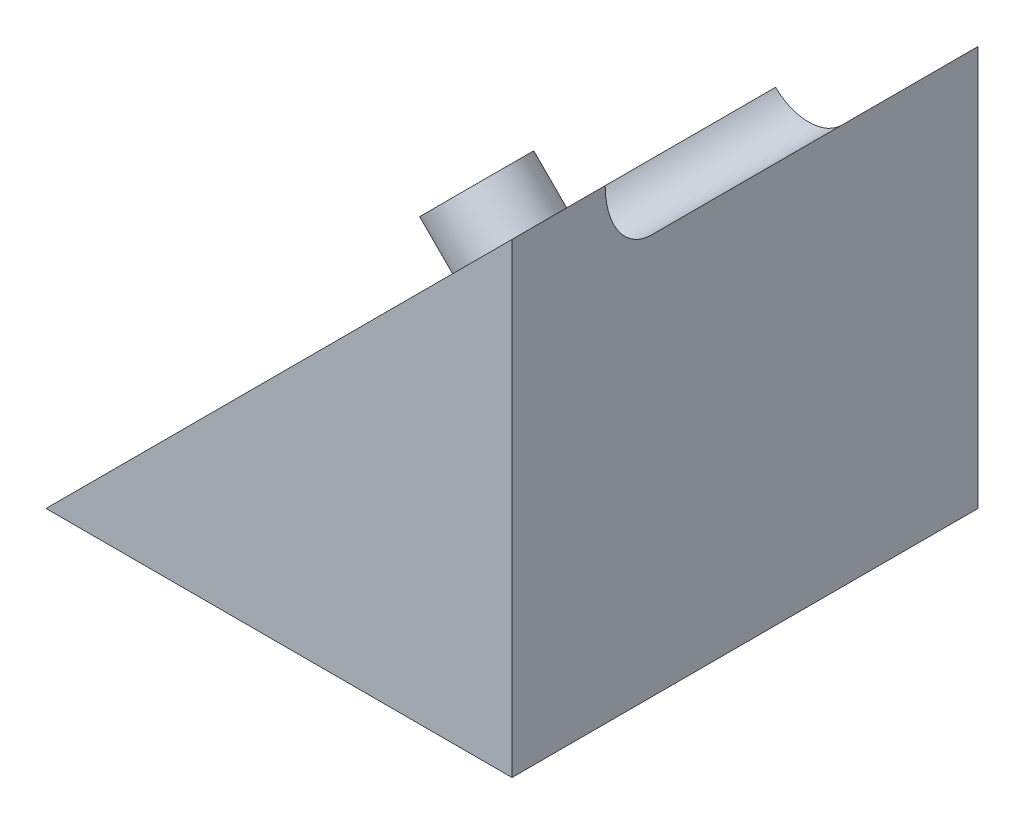
SolidWorks part; units mm, degrees
ref_plane "Front Plane" through (0, 0, 0) normal (0, 0, 1) x (1, 0, 0)
ref_plane "Top Plane" through (0, 0, 0) normal (0, 1, 0) x (1, 0, 0)
ref_plane "Right Plane" through (0, 0, 0) normal (1, 0, 0) x (0, 0, -1)
sketch "Sketch1" plane through (0, 0, 0) normal (0, 0, 1) x (1, 0, 0)
  line L0 (0, 0) -> (5, 5)
  line L1 (5, 5) -> (5, 0)
  line L2 (5, 0) -> (0, 0)
  dimension "D1" = 45
  dimension "D2" = 5
extrude "Boss-Extrude1" add sketch "Sketch1" along normal blind 5
ref_plane "Plane1" through (2.5, 2.5, 0) normal (0.7071, 0.7071, 0) x (0, 0, -1)
sketch "Sketch2" plane through (2.5, 2.5, 0) normal (0.7071, 0.7071, 0) x (0, 0, -1)
  line L0 (0, 0) -> (-5, 0) construction
  circle A0 centre (-3.5, 0) radius 0.5
  dimension "D1" = 1
  dimension "D2" = 3.5
extrude "Cut-Extrude1" cut sketch "Sketch2" against normal through all both and the other way through all
sketch "Sketch3" plane through (0, 0, 0) normal (-0.7071, 0.7071, 0) x (0, 0, 1)
  line L0 (5, 0) -> (4, 0) construction
  line L1 (0, 7.0711) -> (3.5, 7.0711)
  line L2 (0, 7.0711) -> (0, 4)
  line L3 (0, 4) -> (3.5, 4)
  line L4 (3.5, 7.0711) -> (3.5, 4)
  line L6 (0, 7.0711) -> (0, 0) construction
  arc A0 (3, 7.0711) -> (4, 7.0711) centre (3.5, 7.0711) ccw construction
  dimension "D1" = 4
extrude "Cut-Extrude3" cut sketch "Sketch3" against normal blind 0.5
fillet "Fillet1" radius 0.5 1 edges at (3.182, 2.4749, 1.75)
fillet "Fillet2" radius 0.5 1 edges at (3.182, 2.682, 3.1464)
sketch "Sketch7" plane through (0, 0, 0) normal (-0.7071, 0.7071, 0) x (0, 0, 1)
  circle A0 centre (2.5, 3.5) radius 0.5
  arc A1 (3, 3.5) -> (2.5, 4) centre (2.5, 3.5) ccw construction
extrude "Boss-Extrude2" add sketch "Sketch7" along normal blind 0.5
